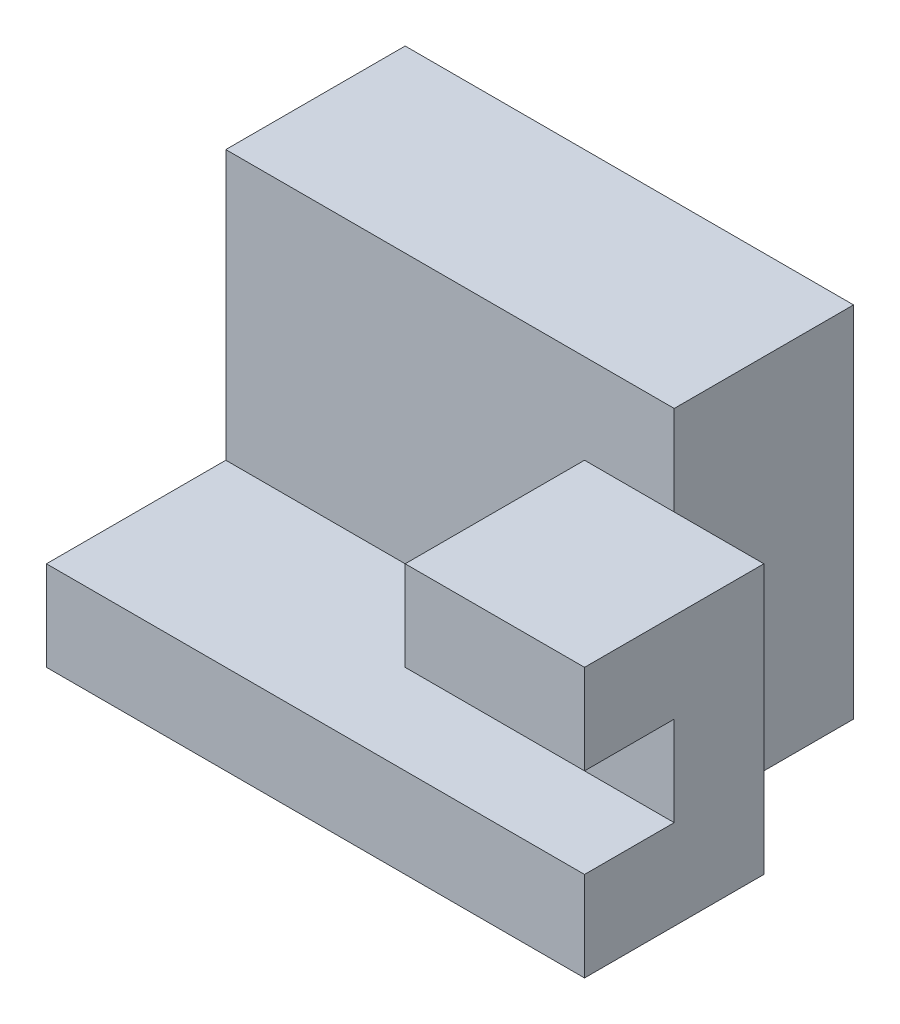
SolidWorks part; units mm, degrees
ref_plane "前基準面" through (0, 0, 0) normal (0, 0, 1) x (1, 0, 0)
ref_plane "上基準面" through (0, 0, 0) normal (0, 1, 0) x (1, 0, 0)
ref_plane "右基準面" through (0, 0, 0) normal (1, 0, 0) x (0, 0, -1)
sketch "草圖1" plane through (0, 0, 0) normal (0, 1, 0) x (1, 0, 0)
  line L0 (0, 0) -> (0, 2)
  line L1 (0, 2) -> (5, 2)
  line L2 (5, 2) -> (5, 0)
  line L3 (5, 0) -> (0, 0)
  line L4 (0, 0) -> (0, -2)
  line L5 (0, -2) -> (6, -2)
  line L6 (6, -2) -> (6, 0)
  line L7 (6, 0) -> (5, 0)
  dimension "D1" = 5
  dimension "D2" = 2
  dimension "D3" = 2
  dimension "D4" = 6
extrude "填料-伸長1" add sketch "草圖1" along normal blind 4 contours L3 L2 L1 L0 region at (2.5, 0, -1)
extrude "填料-伸長2" add sketch "草圖1<3>" along normal blind 1 contours L6 L7 L3 L4 L5 region at (3, 0, 1)
sketch "草圖1<3>" plane through (0, 0, 0) normal (0, 1, 0) x (1, 0, 0) same geometry as "草圖1"
sketch "草圖2" plane through (6, 0, 0) normal (1, 0, 0) x (0, 0, -1)
  line L0 (0, 1) -> (0, 11.3509)
  line L1 (0, 4) -> (0, 1) construction
  line L2 (-1, 2) -> (-2, 2)
  line L3 (-2, 2) -> (-2, 3)
  line L4 (-2, 3) -> (0, 3)
  line L5 (-1, 2) -> (-1, 1)
  line L6 (-2, 1) -> (0, 1) construction
  line L7 (-1, 1) -> (-2, 1)
  line L8 (-2, 1) -> (-2, 0)
  line L9 (-2, 0) -> (0, 0)
  line L10 (2, 4) -> (0, 4) construction
  line L11 (-1, 1) -> (-2, 1)
  line L12 (-2, 0) -> (0, 0)
  line L13 (0, 3) -> (0, 0)
  line M7 (0, 1) -> (-2, 1)
  dimension "D1" = 1
  dimension "D2" = 2
  dimension "D3" = 1
  dimension "D4" = 1
extrude "填料-伸長3" add sketch "草圖2" against normal blind 2 contours L13 L4 L3 L2 L5 L0 M7 region at (6, 2.1667, 0.8333)
